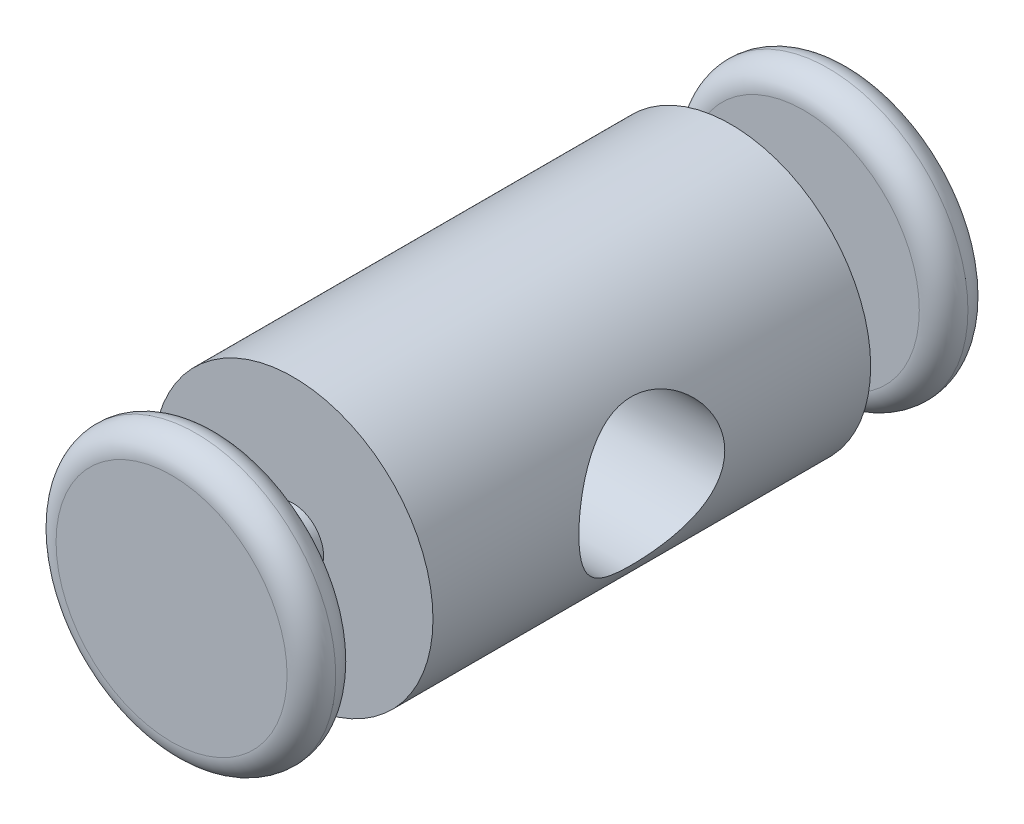
SolidWorks part; units mm, degrees
ref_plane "Front Plane" through (0, 0, 0) normal (0, 0, 1) x (1, 0, 0)
ref_plane "Top Plane" through (0, 0, 0) normal (0, 1, 0) x (1, 0, 0)
ref_plane "Right Plane" through (0, 0, 0) normal (1, 0, 0) x (0, 0, -1)
sketch "Sketch1" plane through (0, 0, 0) normal (0, 0, 1) x (1, 0, 0)
  circle A0 centre (0, 0) radius 11.5
  dimension "D1" = 23
extrude "Boss-Extrude1" add sketch "Sketch1" along normal blind 18
sketch "Sketch2" plane through (0, 0, 18) normal (0, 0, 1) x (1, 0, 0)
  circle A0 centre (0, 0) radius 2.5
  dimension "D1" = 5
extrude "Boss-Extrude2" add sketch "Sketch2" along normal blind 6
sketch "Sketch3" plane through (0, 0, 24) normal (0, 0, 1) x (1, 0, 0)
  circle A1 centre (0, 0) radius 11.5
  circle A3 centre (0, 0) radius 11.5
  dimension "D1" = 0
extrude "Boss-Extrude3" add sketch "Sketch3" along normal blind 4
fillet "Fillet1" radius 2 2 edges at (11.5, 0, 24) (11.5, 0, 28)
mirror "Mirror1" about plane through (0, 0, 0) normal (0, 0, 1) of bodies 103 104
sketch "Sketch5" plane through (0, 0, 0) normal (1, 0, 0) x (0, 0, -1)
  circle A0 centre (0, 0) radius 6
  dimension "D1" = 12
extrude "Cut-Extrude2" cut sketch "Sketch5" against normal through all both and the other way through all
